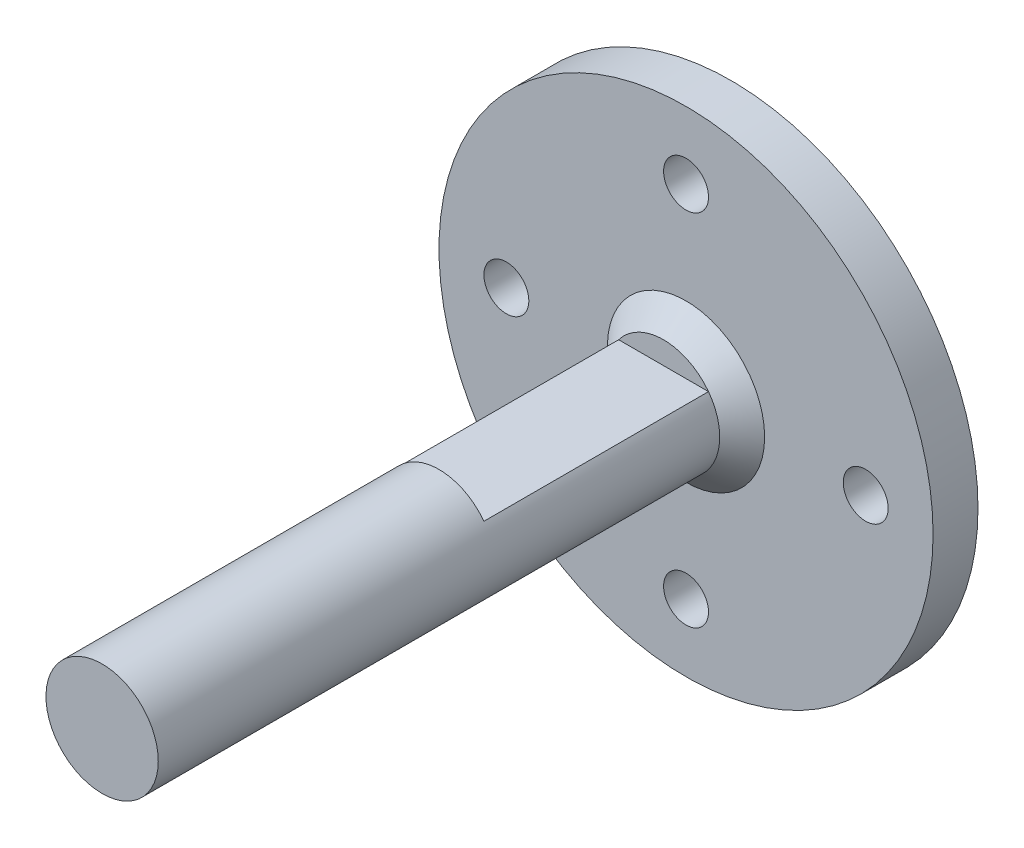
SolidWorks part; units mm, degrees
material "Chromowa stal nierdzewna"
ref_plane "Płaszczyzna przednia" through (0, 0, 0) normal (0, 0, 1) x (1, 0, 0)
ref_plane "Płaszczyzna górna" through (0, 0, 0) normal (0, 1, 0) x (1, 0, 0)
ref_plane "Płaszczyzna prawa" through (0, 0, 0) normal (1, 0, 0) x (0, 0, -1)
sketch "Szkic1" plane through (0, 0, 0) normal (0, 0, 1) x (1, 0, 0)
  circle A0 centre (0, 0) radius 11
  circle A1 centre (0, 8) radius 1
  circle A2 centre (8, 0) radius 1
  circle A3 centre (0, -8) radius 1
  circle A4 centre (-8, 0) radius 1
  point P14 (0, 0)
  dimension "D1" = 22
  dimension "D2" = 2
  dimension "D3" = 8
  dimension "D4" = 4
extrude "Dodanie-wyciągnięcie1" add sketch "Szkic1" along normal blind 2
sketch "Szkic2" plane through (0, 0, 2) normal (0, 0, 1) x (1, 0, 0)
  circle A0 centre (0, 0) radius 2.5
  dimension "D1" = 5
extrude "Dodanie-wyciągnięcie2" add sketch "Szkic2" along normal blind 26
sketch "Szkic3" plane through (0, 0, 28) normal (0, 0, 1) x (1, 0, 0)
  line L1 (2, 1.5) -> (-2, 1.5)
  arc A0 (2, 1.5) -> (-2, 1.5) centre (0, 0) ccw
extrude "Wytnij-wyciągnięcie1" cut sketch "Szkic3" against normal blind 10 from offset 15 offset against normal yes
chamfer "Sfazowanie1" distance 1 angle 45 1 edges at (2.5, 0, 2)
